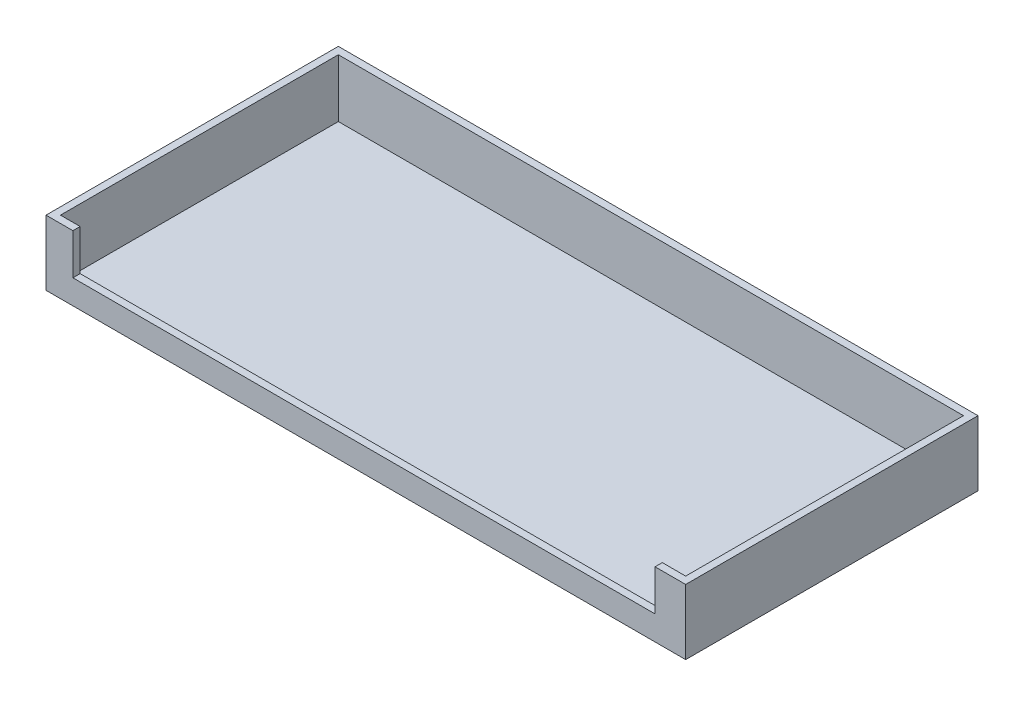
SolidWorks part; units mm, degrees
ref_plane "Front Plane" through (0, 0, 0) normal (0, 0, 1) x (1, 0, 0)
ref_plane "Top Plane" through (0, 0, 0) normal (0, 1, 0) x (1, 0, 0)
ref_plane "Right Plane" through (0, 0, 0) normal (1, 0, 0) x (0, 0, -1)
sketch "Sketch1" plane through (0, 0, 0) normal (0, 1, 0) x (1, 0, 0)
  line L0 (-110.5, -50.5) -> (-110.5, 50.5)
  line L1 (-108, -48) -> (108, -48)
  line L2 (-108, -48) -> (-108, 48)
  line L3 (-108, 48) -> (108, 48)
  line L4 (108, -48) -> (108, 48)
  line L5 (-108, -48) -> (108, 48) construction
  line L6 (-108, 48) -> (108, -48) construction
  line L7 (-110.5, 50.5) -> (110.5, 50.5)
  line L8 (110.5, -50.5) -> (110.5, 50.5)
  line L9 (-110.5, -50.5) -> (110.5, -50.5)
  point P0 (0, 0)
  dimension "D1" = 216
  dimension "D2" = 96
  dimension "D3" = 2.5
extrude "Boss-Extrude1" add sketch "Sketch1" along normal blind 20 contours L0 L9 L8 L7 L4 L1 L2 L3 region at (-108.0701, 0, 0)
extrude "Boss-Extrude2" add sketch "Sketch1<3>" against normal blind 2.5 contours L0 L7 L8 L9
sketch "Sketch1<3>" plane through (0, 0, 0) normal (0, 1, 0) x (1, 0, 0) same geometry as "Sketch1"
ref_plane "Plane1" through (-110.5, 20, 50.5) normal (1, 0, 0) x (0, 0, -1)
sketch "Sketch3" plane through (0, 0, 50.5) normal (0, 0, 1) x (1, 0, 0)
  line L0 (-110.5, 20) -> (110.5, 20) construction
  line L1 (-101.2008, 20) -> (99.9204, 20)
  line L2 (-101.2008, 20) -> (-101.2008, 5.8947)
  line L3 (-101.2008, 5.8947) -> (99.9204, 5.8947)
  line L4 (99.9204, 20) -> (99.9204, 5.8947)
extrude "Cut-Extrude1" cut sketch "Sketch3" against normal blind 10
